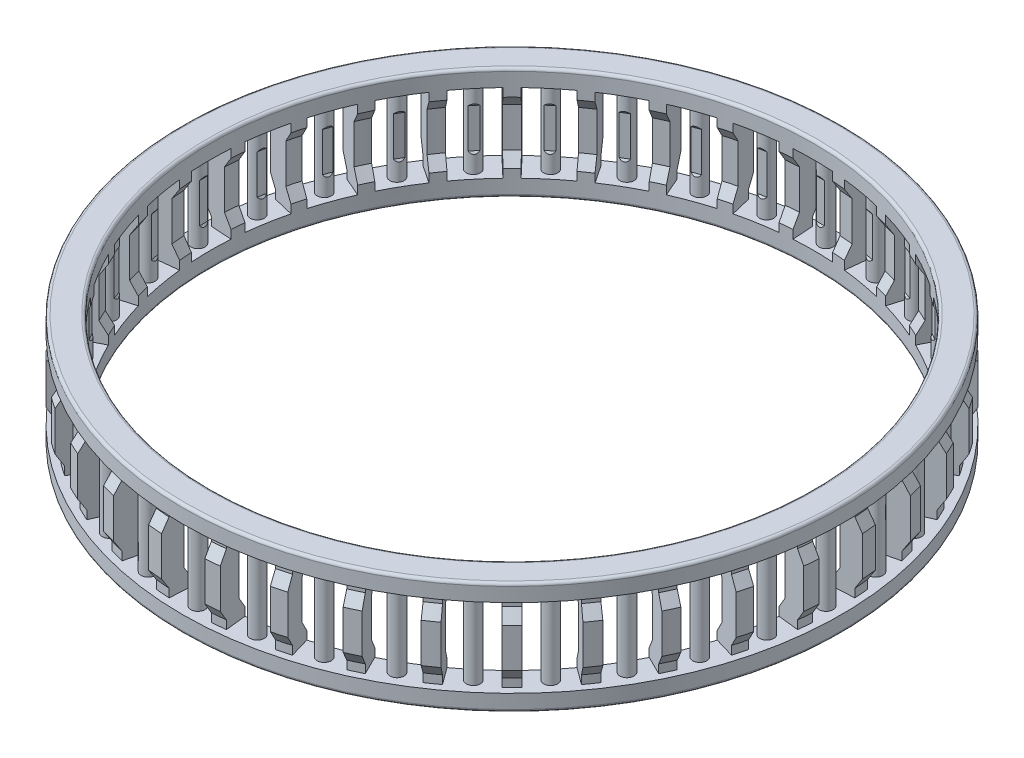
SolidWorks part; units mm, degrees
ref_plane "Front Plane" through (0, 0, 0) normal (0, 0, 1) x (1, 0, 0)
ref_plane "Top Plane" through (0, 0, 0) normal (0, 1, 0) x (1, 0, 0)
ref_plane "Right Plane" through (0, 0, 0) normal (1, 0, 0) x (0, 0, -1)
sketch "Sketch1" plane through (0, 0, 0) normal (0, 0, 1) x (1, 0, 0)
  line L0 (0, 54.2605) -> (0, 0) construction
  line L1 (0, 0) -> (-59.69, 0) construction
  line L2 (-59.69, 6.604) -> (-59.69, 13.716)
  line L3 (-59.69, 13.716) -> (-58.42, 15.748)
  line L4 (-58.42, 15.748) -> (-58.42, 17.272)
  line L5 (-58.42, 17.272) -> (-59.69, 17.272)
  line L6 (-59.69, 17.272) -> (-59.69, 19.812)
  line L7 (-59.182, 20.32) -> (-55.118, 20.32)
  line L8 (-54.61, 19.812) -> (-54.61, 15.748)
  line L9 (-54.61, 15.748) -> (-55.88, 13.716)
  line L10 (-55.88, 13.716) -> (-55.88, 6.604)
  line L11 (-59.69, 10.16) -> (-55.88, 10.16) construction
  line L12 (-54.61, 4.572) -> (-55.88, 6.604)
  line L13 (-54.61, 0.508) -> (-54.61, 4.572)
  line L14 (-59.182, 0) -> (-55.118, 0)
  line L15 (-59.69, 3.048) -> (-59.69, 0.508)
  line L16 (-58.42, 3.048) -> (-59.69, 3.048)
  line L17 (-58.42, 4.572) -> (-58.42, 3.048)
  line L18 (-59.69, 6.604) -> (-58.42, 4.572)
  arc A0 (-55.118, 20.32) -> (-54.61, 19.812) centre (-55.118, 19.812) cw
  arc A1 (-54.61, 0.508) -> (-55.118, 0) centre (-55.118, 0.508) cw
  arc A2 (-59.69, 19.812) -> (-59.182, 20.32) centre (-59.182, 19.812) cw
  arc A3 (-59.182, 0) -> (-59.69, 0.508) centre (-59.182, 0.508) cw
  point P24 (-54.61, 20.32)
  point P27 (-54.61, 0)
  point P30 (-59.69, 20.32)
  point P33 (-59.69, 0)
  dimension "D8" = 0.508
  dimension "D9" = 0.508
  dimension "D1" = 59.69
  dimension "D2" = 10.16
  dimension "D3" = 3.556
  dimension "D4" = 1.524
  dimension "D5" = 5.08
  dimension "D6" = 2.54
  dimension "D7" = 3.048
revolve "Revolve1" add sketch "Sketch1" angle 360 about L0
sketch "Sketch2" plane through (0, 0, 0) normal (0, 1, 0) x (1, 0, 0)
  line L1 (-59.944, 3.937) -> (-59.944, -3.937)
  line L2 (-54.102, -3.57) -> (-54.102, 3.57)
  line L3 (0, 0) -> (0, 24.1639) construction
  line L4 (-59.944, 3.937) -> (-54.102, 3.57)
  line L5 (-59.944, -3.937) -> (-54.102, -3.57)
  line L6 (-54.102, 0) -> (-59.69, 0) construction
  circle A0 centre (0, 0) radius 59.69 construction
  circle A1 centre (-56.896, 0) radius 1.27
  point P9 (-59.944, 0)
  point P10 (-54.102, 0)
  dimension "D5" = 2.54
  dimension "D1" = 59.944
  dimension "D2" = 5.842
  dimension "D3" = 7.874
  dimension "D4" = 7.14
extrude "Cut-Extrude1" cut sketch "Sketch2" along normal up to surface (14.224 mm away) from offset 3.048 up to face at (0, 17.272, 58.42)
pattern_circular "CirPattern2" count 36 over 360 about axis through (0, 0, 0) along (0, 1, 0) of "Cut-Extrude1"
